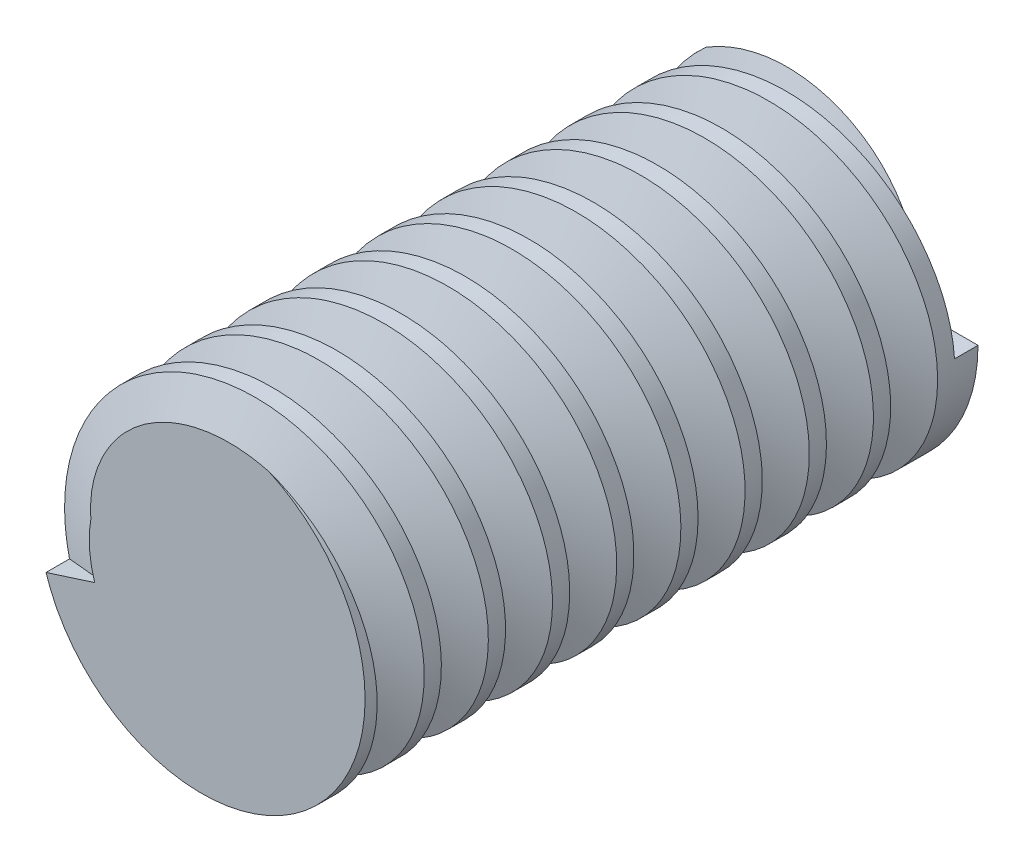
SolidWorks part; units mm, degrees
ref_plane "前视基准面" through (0, 0, 0) normal (0, 0, 1) x (1, 0, 0)
ref_plane "上视基准面" through (0, 0, 0) normal (0, 1, 0) x (1, 0, 0)
ref_plane "右视基准面" through (0, 0, 0) normal (1, 0, 0) x (0, 0, -1)
other "Configuration Table"
sketch "blank" plane through (0, 0, 0) normal (0, 0, 1) x (1, 0, 0)
  circle A0 centre (0, 0) radius 8
  dimension "D1" = 16
extrude "body" add sketch "blank" along normal blind 30
sketch "hxbase" plane through (0, 0, 0) normal (0, 0, 1) x (1, 0, 0)
  circle A0 centre (0, 0) radius 7
  dimension "D1" = 14
curve "hx" pitch 3.1416 height 30 turns 9.5493
sketch "groove" plane through (0, 0, 0) normal (0, 1, 0) x (1, 0, 0)
  line L0 (5.5, 0.2381) -> (5.5, -0.2381)
  line L1 (5.5, -0.2381) -> (8.4, -1.2963)
  line L2 (8.4, -1.2963) -> (8.4, 1.2963)
  line L3 (8.4, 1.2963) -> (5.5, 0.2381)
sweep "thread" cut profiles "groove" path "hx"
